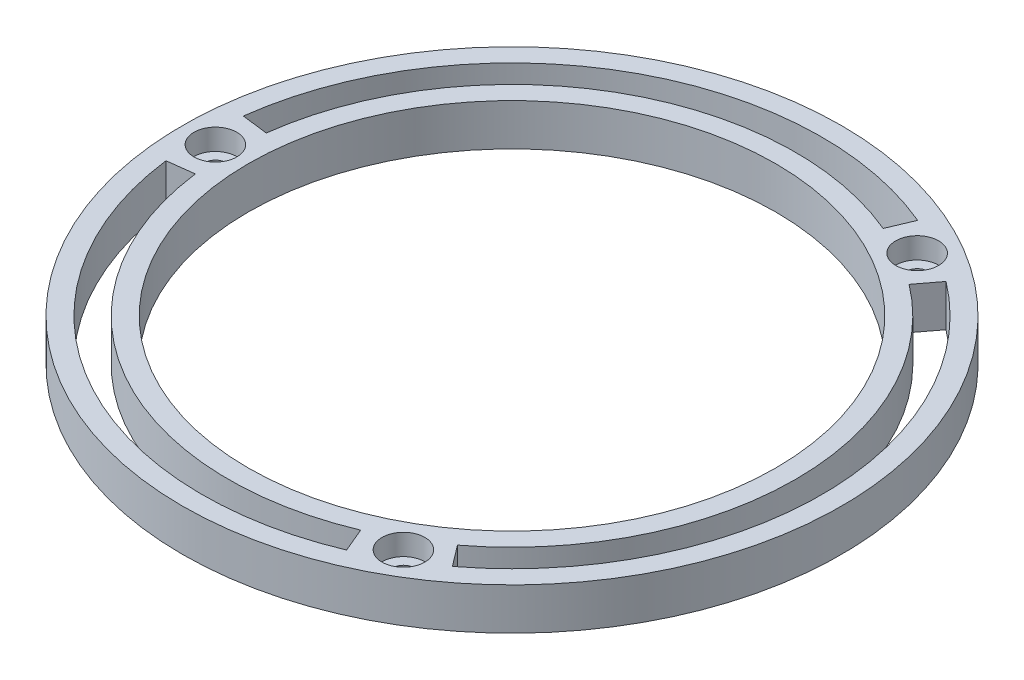
SolidWorks part; units mm, degrees
ref_plane "Front Plane" through (0, 0, 0) normal (0, 0, 1) x (1, 0, 0)
ref_plane "Top Plane" through (0, 0, 0) normal (0, 1, 0) x (1, 0, 0)
ref_plane "Right Plane" through (0, 0, 0) normal (1, 0, 0) x (0, 0, -1)
sketch "Sketch1" plane through (0, 0, 0) normal (0, 1, 0) x (1, 0, 0)
  line L0 (-50, 0) -> (50, 0) construction
  line L1 (-25, 43.3013) -> (25, -43.3013) construction
  line L2 (-25, -43.3013) -> (25, 43.3013) construction
  line L3 (30.2166, 39.8366) -> (24.1733, 31.8693)
  line L4 (19.3913, 46.0866) -> (15.513, 36.8693)
  line L5 (30.2166, -39.8366) -> (24.1733, -31.8693)
  line L6 (19.3913, -46.0866) -> (15.513, -36.8693)
  line L7 (-49.6078, 6.25) -> (-39.6863, 5)
  line L8 (-49.6078, -6.25) -> (-39.6863, -5)
  line L9 (0, 0) -> (15.513, 36.8693) construction
  line L10 (0, 0) -> (24.1733, 31.8693) construction
  line L11 (0, 0) -> (24.1733, -31.8693) construction
  line L12 (0, 0) -> (15.513, -36.8693) construction
  line L13 (0, 0) -> (-39.6863, 5) construction
  line L14 (-39.6863, -5) -> (0, 0) construction
  circle A0 centre (0, 0) radius 50
  circle A1 centre (0, 0) radius 47
  circle A2 centre (0, 0) radius 43
  circle A3 centre (0, 0) radius 40
  point P10 (0, 0)
  point P14 (0, 0)
  point P17 (0, 0)
  dimension "D1" = 100
  dimension "D2" = 3
  dimension "D5" = 60
  dimension "D6" = 60
  dimension "D7" = 5
  dimension "D8" = 5
  dimension "D9" = 5
  dimension "D10" = 5
  dimension "D11" = 5
  dimension "D12" = 5
  dimension "D3" = 4
  dimension "D4" = 3
extrude "Boss-Extrude1" add sketch "Sketch1" along normal blind 6.35 contours A1 L5 A0 L3 | A3 L5 A2 L3 | A3 L6 A2 L5 | A2 L6 A1 L5 | A1 L6 A0 L5 | A1 L8 A0 L6 | A3 L8 A2 L6 | A3 L7 A2 L8 | A2 L7 A1 L8 | A1 L7 A0 L8 | A1 L4 A0 L7 | A3 L4 A2 L7 | A3 L3 A2 L4 | A2 L3 A1 L4 | A1 L3 A0 L4 region at (44.0425, 0, -21.8721) region at (24.1943, 0, -41.9057) region at (22.4559, 0, -38.8948) region at (18.0546, 0, -45.0217) region at (37.876, 0, -18.8097) region at (20.7047, 0, -35.8617) region at (24.1943, 0, 41.9057) region at (-48.3886, 0, 0) region at (15.4453, 0, -38.5252) region at (22.4559, 0, 38.8948) region at (-44.9118, 0, 0) region at (-24.5905, 0, 42.592) region at (20.7047, 0, 35.8617) region at (-41.4095, 0, 0) region at (-21.1477, 0, 36.6289)
sketch "Sketch2" plane through (0, 6.35, 0) normal (0, 1, 0) x (1, 0, 0)
  line L1 (25, 43.3013) -> (20, 34.641) construction
  line L2 (20, -34.641) -> (25, -43.3013) construction
  line L3 (0, 0) -> (25.9863, -34.2595) construction
  line L4 (0, 0) -> (-40, 0) construction
  line L6 (0, 0) -> (20, -34.641) construction
  line L7 (-40, 0) -> (-50, 0) construction
  line L8 (0, 0) -> (20, 34.641) construction
  line L9 (0, 0) -> (16.6765, 39.6345) construction
  circle A0 centre (-45, 0) radius 1.65
  circle A1 centre (22.5, -38.9711) radius 1.65
  circle A2 centre (22.5, 38.9711) radius 1.65
  circle A3 centre (0, 0) radius 40 construction
  circle A4 centre (0, 0) radius 50 construction
  dimension "D1" = 3.3
  dimension "D2" = 5
  dimension "D3" = 5
extrude "M3-holes" cut sketch "Sketch2" against normal up to next
sketch "Sketch3" plane through (0, 6.35, 0) normal (0, 1, 0) x (1, 0, 0)
  circle A0 centre (-45, 0) radius 3.25
  circle A1 centre (22.5, 38.9711) radius 3.25
  circle A2 centre (22.5, -38.9711) radius 3.25
  dimension "D1" = 6.5
extrude "Cut-Extrude1" cut sketch "Sketch3" against normal blind 3.2
